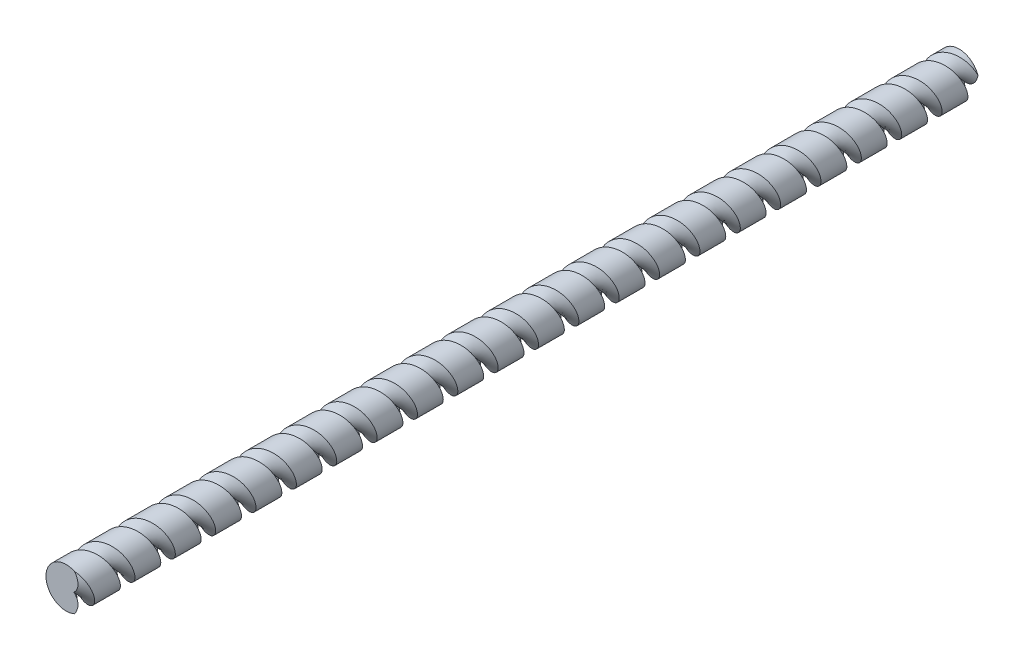
SolidWorks part; units mm, degrees
ref_plane "Alzado" through (0, 0, 0) normal (0, 0, 1) x (1, 0, 0)
ref_plane "Planta" through (0, 0, 0) normal (0, 1, 0) x (1, 0, 0)
ref_plane "Vista lateral" through (0, 0, 0) normal (1, 0, 0) x (0, 0, -1)
sketch "Croquis1" plane through (0, 0, 0) normal (0, 0, 1) x (1, 0, 0)
  circle A0 centre (0, 0) radius 4
  dimension "D1" = 8
extrude "Saliente-Extruir1" add sketch "Croquis1" along normal blind 177
sketch "Croquis2" plane through (0, 0, 177) normal (0, 0, 1) x (1, 0, 0)
  circle A1 centre (0, 0) radius 4
  circle A2 centre (0, 0) radius 4
  dimension "D1" = 0
curve "Hélice/Espiral1" pitch 8 height 480 turns 60
sketch "Croquis4" plane through (0, 0, 0) normal (0, 1, 0) x (1, 0, 0)
  line L4 (4, -177) -> (4, -175.5566)
  line L5 (4, -177) -> (4, 0) construction
  line L6 (4, -175.5566) -> (1.5, -177)
  line L7 (-4, -177) -> (4, -177) construction
  line L8 (1.5, -177) -> (4, -178.4434)
  line L9 (4, -178.4434) -> (4, -177)
  dimension "D1" = 60
  dimension "D2" = 60
  dimension "D3" = 2.5
sweep "Cortar-Barrer2" cut profiles "Croquis4" path "Hélice/Espiral1"
